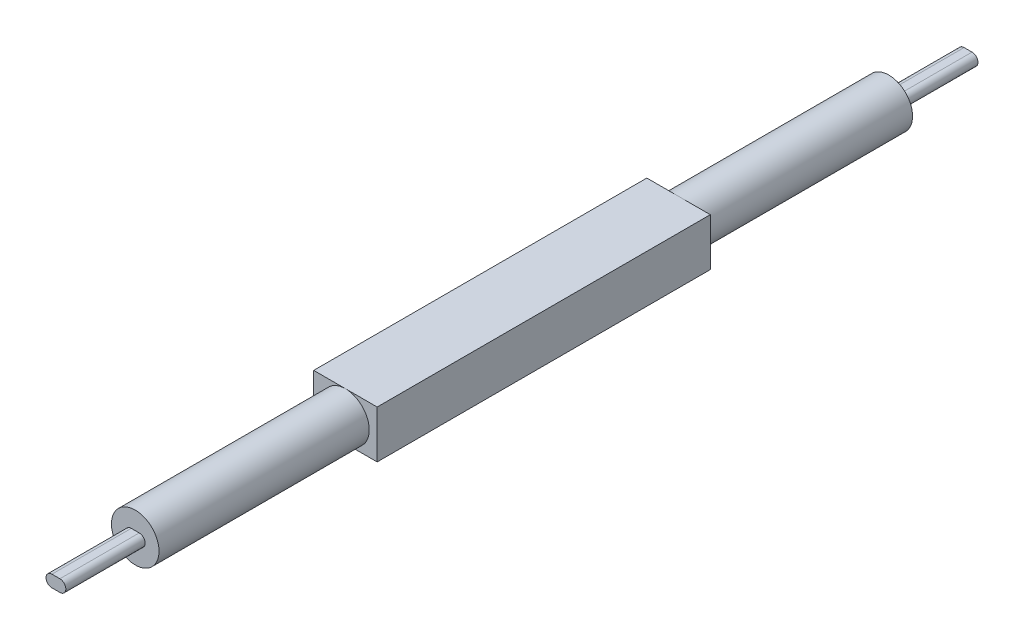
SolidWorks part; units mm, degrees
ref_plane "Front Plane" through (0, 0, 0) normal (0, 0, 1) x (1, 0, 0)
ref_plane "Top Plane" through (0, 0, 0) normal (0, 1, 0) x (1, 0, 0)
ref_plane "Right Plane" through (0, 0, 0) normal (1, 0, 0) x (0, 0, -1)
sketch "Esquisse1" plane through (0, 0, 0) normal (0, 0, 1) x (1, 0, 0)
  circle A0 centre (0, 0) radius 6
  dimension "D1" = 12
extrude "Boss.-Extru.1" add sketch "Esquisse1" along normal blind 190
sketch "Esquisse2" plane through (0, 0, 190) normal (0, 0, 1) x (1, 0, 0)
  line L0 (-1, 0) -> (1, 0) construction
  line L1 (-1, 1.5) -> (1, 1.5)
  line L2 (-1, -1.5) -> (1, -1.5)
  arc A0 (-1, 1.5) -> (-1, -1.5) centre (-1, 0) ccw
  arc A1 (1, -1.5) -> (1, 1.5) centre (1, 0) ccw
  circle A2 centre (0, 0) radius 6 construction
  point P3 (0, 0)
  dimension "D2" = 1.5
  dimension "D1" = 2
extrude "Boss.-Extru.2" add sketch "Esquisse2" along normal blind 20
sketch "Esquisse3" plane through (0, 0, 0) normal (0, 0, -1) x (-1, 0, 0)
  line L0 (-1, 0) -> (1, 0) construction
  line L1 (-1, 1.5) -> (1, 1.5)
  line L2 (-1, -1.5) -> (1, -1.5)
  arc A0 (-1, 1.5) -> (-1, -1.5) centre (-1, 0) ccw
  arc A1 (1, -1.5) -> (1, 1.5) centre (1, 0) ccw
  circle A2 centre (0, 0) radius 6 construction
  point P4 (0, 0)
  dimension "D2" = 1.5
  dimension "D1" = 2
extrude "Boss.-Extru.3" add sketch "Esquisse3" along normal blind 20
ref_plane "Plan1" through (0, -6, 0) normal (0, -1, 0) x (-1, 0, 0)
sketch "Esquisse4" plane through (0, -6, 0) normal (0, -1, 0) x (-1, 0, 0)
  line L0 (0, 0) -> (1, -190) construction
  line L3 (6, 0) -> (6, -36.0548) construction
  line L4 (-5, -52) -> (6, -52)
  line L5 (-5, -52) -> (-5, -138)
  line L6 (-5, -138) -> (6, -138)
  line L7 (6, -52) -> (6, -138)
  line L8 (-5, -52) -> (6, -138) construction
  line L9 (-5, -138) -> (6, -52) construction
  line L10 (6, -190) -> (6, 0) construction
  point P4 (0.5, -95)
  point P5 (0.5, -95)
  dimension "D1" = 95
  dimension "D2" = 95
  dimension "D3" = 86
ref_axis "Axe1" through (0, 0, 209.728) along (0, 0, -1)
ref_plane "Plan2" through (0, 0, 0) normal (-1, 0, 0) x (0, 0, -1)
sketch "Esquisse5" plane through (0, 0, 0) normal (-1, 0, 0) x (0, 0, -1)
  line L0 (-190, 0) -> (0, 0) construction
  line L1 (-209.728, 0) -> (-19.728, 0) construction
  line L2 (0, -6) -> (0, 6) construction
  line L3 (-190, -6) -> (0, -6) construction
  line L4 (-190, -6) -> (-125.6115, -6) construction
  line L5 (-190, 6) -> (-190, -6) construction
  line L6 (-216.5933, 0) -> (23.9212, 0) construction
  line L7 (-137, 6) -> (-53, 6)
  line L8 (-137, 6) -> (-137, -6)
  line L10 (-53, 6) -> (-53, -6)
  line L11 (-137, 6) -> (-53, -6) construction
  line L12 (-137, -6) -> (-53, 6) construction
  line L13 (-190, 6) -> (46.3906, 6) construction
  line L14 (0, 6) -> (-190, 6) construction
  line L15 (6.6, 6) -> (-6.6, 6) construction
  line L17 (-137, -6) -> (-53, -6)
  point P5 (-95, 0)
  point P8 (-95, 0)
  dimension "D1" = 190
  dimension "D2" = 95
  dimension "D3" = 95
  dimension "D4" = 84
extrude "Boss.-Extru.5" add sketch "Esquisse5" along normal blind 8 and the other way blind 8
